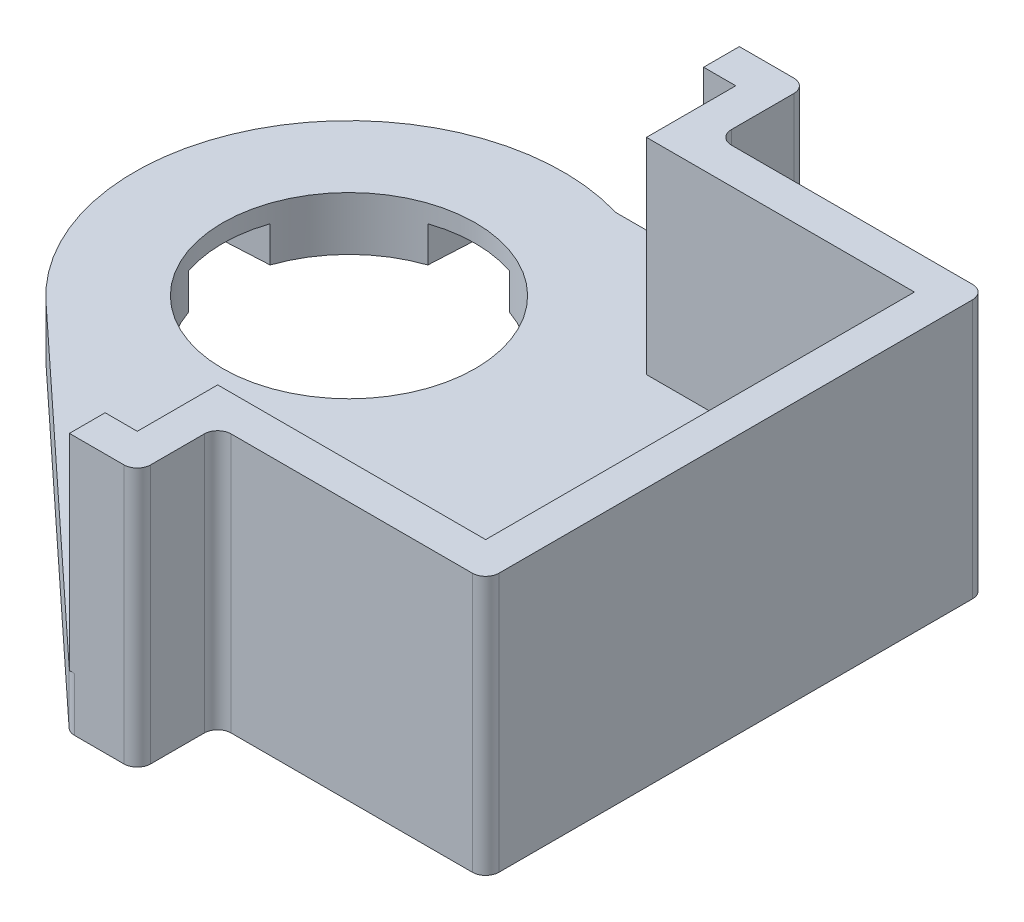
SolidWorks part; units mm, degrees
ref_plane "Front Plane" through (0, 0, 0) normal (0, 0, 1) x (1, 0, 0)
ref_plane "Top Plane" through (0, 0, 0) normal (0, 1, 0) x (1, 0, 0)
ref_plane "Right Plane" through (0, 0, 0) normal (1, 0, 0) x (0, 0, -1)
sketch "Sketch1" plane through (0, 0, 0) normal (0, 1, 0) x (1, 0, 0)
  line L0 (3.35, 28) -> (3.35, 23)
  line L9 (0, 0) -> (3.35, 0)
  line L10 (0, 0) -> (0, 23)
  line L11 (0, 23) -> (3.35, 23)
  line L12 (19.65, 0) -> (19.65, 23)
  line L14 (4.65, 0) -> (4.65, -5)
  line L15 (4.65, -5) -> (3.35, -5)
  line L16 (3.35, 0) -> (3.35, -5)
  line L17 (4.65, -5) -> (3.35, -5)
  line L18 (4.65, -5) -> (4.65, 28) construction
  line L19 (4.65, 28) -> (3.35, 28)
  line L20 (3.35, -5) -> (3.35, 28) construction
  line L21 (4.65, 28) -> (4.65, 23)
  line L22 (4.65, 0) -> (19.65, 0)
  line L23 (4.65, 23) -> (19.65, 23)
  line L24 (2.85, 28) -> (2.85, 23.5)
  line L25 (-0.5, 23.5) -> (2.85, 23.5)
  line L26 (-0.5, -0.5) -> (-0.5, 23.5)
  line L27 (-0.5, -0.5) -> (2.85, -0.5)
  line L28 (2.85, -0.5) -> (2.85, -5)
  line L29 (5.15, -0.5) -> (5.15, -5)
  line L30 (5.15, -0.5) -> (20.15, -0.5)
  line L31 (20.15, -0.5) -> (20.15, 23.5)
  line L32 (5.15, 23.5) -> (20.15, 23.5)
  line L33 (5.15, 28) -> (5.15, 23.5)
  line L34 (4.65, -4.5) -> (3.35, -4.5)
  line L35 (4.65, -4.5) -> (3.35, -4.5)
  line L37 (5.15, -5) -> (5.15, 28)
  line L38 (3.85, -5) -> (3.85, 28)
  line L39 (2.85, -5) -> (3.35, -5)
  line L40 (5.15, -5) -> (4.65, -5)
  line L41 (3.35, 28) -> (5.15, 28)
  line L42 (4.65, 28) -> (3.35, 28)
  line L43 (5.15, 28) -> (5.15, 28.5)
  line L46 (2.85, 28) -> (2.85, 28.5)
  line L47 (2.85, 28.5) -> (5.15, 28.5)
  line L48 (5.15, 28) -> (5.15, 28.5)
  dimension "D1" = 23
  dimension "D2" = 19.65
  dimension "D3" = 15
  dimension "D4" = 1.3
  dimension "D5" = 5
  dimension "D6" = 5
  dimension "D7" = 0.5
sketch "Sketch3" plane through (0, 0, 0) normal (0, 1, 0) x (1, 0, 0)
  line L1 (3.35, -5) -> (7.15, -5)
  line L2 (3.35, -5) -> (3.35, 28)
  line L3 (3.35, 28) -> (7.15, 28)
  line L4 (7.15, -5) -> (7.15, -2.5)
  line L5 (4.65, 28) -> (3.35, 28) construction
  line L6 (7.15, 25.5) -> (7.15, 28)
  line L7 (4.65, -5) -> (3.35, -5) construction
  line L8 (7.15, 25.5) -> (22.15, 25.5)
  line L10 (7.15, -2.5) -> (22.15, -2.5)
  line L11 (22.15, 25.5) -> (22.15, -2.5)
  line L12 (4.65, 23) -> (19.65, 23) construction
  line L13 (19.65, 0) -> (19.65, 23) construction
  line L14 (4.65, 0) -> (19.65, 0) construction
  line L15 (4.65, 0) -> (4.65, -5) construction
  point P20 (7.15, -3.75)
  dimension "D1" = 2.5
  dimension "D2" = 2.5
  dimension "D3" = 2.5
  dimension "D4" = 2.5
sketch "Sketch9" plane through (0, 0, 0) normal (0, 1, 0) x (1, 0, 0)
  line L0 (3.35, 28) -> (3.35, 23)
  line L9 (0, 0) -> (3.35, 0)
  line L10 (0, 0) -> (0, 23)
  line L11 (0, 23) -> (3.35, 23)
  line L12 (19.65, 0) -> (19.65, 23)
  line L14 (4.65, 0) -> (4.65, -4.5)
  line L15 (4.65, -5) -> (3.35, -5)
  line L16 (3.35, 0) -> (3.35, -4.5)
  line L17 (4.65, -5) -> (3.35, -5)
  line L18 (4.65, -4.5) -> (4.65, 28) construction
  line L19 (4.65, 28) -> (3.35, 28)
  line L20 (3.35, -4.5) -> (3.35, 28) construction
  line L21 (4.65, 28) -> (4.65, 23)
  line L22 (4.65, 0) -> (19.65, 0)
  line L23 (4.65, 23) -> (19.65, 23)
  line L24 (4.65, 28) -> (3.35, 28)
  line L25 (5.15, -5) -> (3.35, -5)
  line L26 (7.15, -5) -> (7.15, -6.25)
  line L27 (6.4, -7) -> (3.35, -7)
  line L28 (3.35, -5) -> (3.35, -7)
  line L29 (5.15, -0.5) -> (5.15, -5)
  line L30 (5.15, -0.5) -> (20.15, -0.5)
  line L31 (20.15, -0.5) -> (20.15, 23.5)
  line L32 (5.15, 23.5) -> (20.15, 23.5)
  line L33 (5.15, 28) -> (5.15, 23.5)
  line L34 (4.65, -4.5) -> (3.35, -4.5)
  line L35 (4.65, -4.5) -> (3.35, -4.5)
  line L36 (7.15, 28) -> (7.15, 26.25)
  line L37 (5.15, -5) -> (5.15, -0.5)
  line L38 (3.35, -5) -> (3.35, -7)
  line L40 (5.15, -5) -> (4.65, -5)
  line L41 (3.35, 28) -> (4.65, 28)
  line L42 (4.65, 28) -> (3.35, 28)
  line L43 (5.15, 28) -> (5.15, 28.5)
  line L47 (3.35, 30.5) -> (5.15, 30.5)
  line L48 (5.15, 28) -> (5.15, 28.5)
  line L49 (7.9, 25.5) -> (21.4, 25.5)
  line L50 (22.15, -1.75) -> (22.15, 24.75)
  line L51 (7.9, -2.5) -> (21.4, -2.5)
  line L52 (7.15, -3.25) -> (7.15, -5)
  line L53 (5.15, 23.5) -> (5.15, 28)
  line L54 (7.15, 28) -> (7.15, 29.75)
  line L55 (6.4, 30.5) -> (3.35, 30.5)
  line L57 (5.15, -5) -> (5.15, 28) construction
  line L58 (7.15, -2.5) -> (22.15, -2.5) construction
  line L60 (3.35, 30.5) -> (5.15, 30.5)
  line L61 (3.35, 30.5) -> (3.35, 28.5)
  line L62 (3.35, 28.5) -> (5.15, 28.5)
  line L64 (4.65, 0) -> (4.65, -5) construction
  line L65 (4.65, -5) -> (4.65, 28) construction
  line L66 (7.15, -2.5) -> (7.15, -5) construction
  line L67 (7.15, 28) -> (7.15, 25.5) construction
  line L68 (7.15, 25.5) -> (22.15, 25.5) construction
  line L69 (22.15, -2.5) -> (22.15, 25.5) construction
  arc A0 (7.9, -2.5) -> (7.15, -3.25) centre (7.9, -3.25) ccw
  arc A1 (7.15, 26.25) -> (7.9, 25.5) centre (7.9, 26.25) ccw
  arc A2 (7.15, 29.75) -> (6.4, 30.5) centre (6.4, 29.75) ccw
  arc A3 (21.4, 25.5) -> (22.15, 24.75) centre (21.4, 24.75) cw
  arc A4 (22.15, -1.75) -> (21.4, -2.5) centre (21.4, -1.75) cw
  arc A5 (7.15, -6.25) -> (6.4, -7) centre (6.4, -6.25) cw
  dimension "D10" = 0.75
  dimension "D1" = 23
  dimension "D2" = 19.65
  dimension "D3" = 15
  dimension "D4" = 1.3
  dimension "D5" = 5
  dimension "D6" = 5
  dimension "D7" = 0.5
  dimension "D8" = 2.5
  dimension "D9" = 2
  dimension "D11" = 0.5
extrude "Bracket" add sketch "Sketch9" along normal blind 11.5 contours L61 L62 L43 L33 L32 L31 L30 L29 L25 L15 L28 L27 L26 L52 L51 L50 L49 L36 L54 L55 L47 region at (4.9, 0, 5.4195)
sketch "Sketch12" plane through (0, 0, 0) normal (0, 1, 0) x (1, 0, 0)
  line L0 (3.1341, -6.7994) -> (-15.1691, 10.209)
  line L2 (-3.4667, 30.5) -> (6.4, 30.5)
  line L3 (7.15, 29.75) -> (7.15, 26.25)
  line L4 (7.9, 25.5) -> (21.4, 25.5)
  line L5 (22.15, 24.75) -> (22.15, -1.75)
  line L6 (21.4, -2.5) -> (7.9, -2.5)
  line L7 (7.15, -3.25) -> (7.15, -6.25)
  line L8 (6.4, -7) -> (3.6447, -7)
  arc A0 (-3.6746, 30.5294) -> (-15.1691, 10.209) centre (-7.0005, 18.9995) ccw
  arc A1 (3.1341, -6.7994) -> (3.6447, -7) centre (3.6447, -6.25) ccw
  arc A2 (7.15, -6.25) -> (6.4, -7) centre (6.4, -6.25) cw
  arc A3 (7.9, -2.5) -> (7.15, -3.25) centre (7.9, -3.25) ccw
  arc A4 (22.15, -1.75) -> (21.4, -2.5) centre (21.4, -1.75) cw
  arc A5 (21.4, 25.5) -> (22.15, 24.75) centre (21.4, 24.75) cw
  arc A6 (7.15, 26.25) -> (7.9, 25.5) centre (7.9, 26.25) ccw
  arc A7 (6.4, 30.5) -> (7.15, 29.75) centre (6.4, 29.75) cw
  arc A8 (-3.4667, 30.5) -> (-3.6746, 30.5294) centre (-3.4667, 31.25) cw
  point P17 (3.35, -7)
  point P22 (7.15, -2.5)
  point P25 (22.15, -2.5)
  point P28 (22.15, 25.5)
  point P31 (7.15, 25.5)
  dimension "D1" = 0.75
extrude "Boss-Extrude1" add sketch "Sketch12" against normal blind 3
sketch "Sketch15" plane through (0, 0, 0) normal (0, 1, 0) x (1, 0, 0)
  line L1 (-4.5, 21.5) -> (4.9995, 21.0005)
  line L2 (-7.0001, 21.5) -> (-7.0005, 30.9995)
  line L5 (-4.5, 21.5) -> (-9.5, 21.5)
  line L7 (-9.5, 21.5) -> (-9.0005, 30.9995)
  line L8 (-4.5, 21.5) -> (-5.0005, 30.9995)
  line L9 (-4.5, 16.5) -> (4.9995, 17.0005)
  line L10 (-4.5, 16.5) -> (-4.5, 21.5)
  line L11 (-4.5, 16.5) -> (-4.9995, 7.0005)
  line L12 (-9.5, 16.5) -> (-8.9995, 7.0005)
  line L13 (-9.5, 16.5) -> (-4.5, 16.5)
  line L14 (-9.5, 16.5) -> (-18.9995, 16.9995)
  line L15 (-9.5, 21.5) -> (-18.9995, 20.9995)
  line L16 (-9.5, 21.5) -> (-9.5, 16.5)
  circle A1 centre (-7, 19) radius 7.0711
  arc A6 (-3.6746, 30.5294) -> (-15.1691, 10.209) centre (-7.0005, 18.9995) ccw construction
  arc A7 (-9.0005, 30.9995) -> (-5.0005, 30.9995) centre (-7.0005, 30.9995) cw
  arc A8 (4.9995, 21.0005) -> (4.9995, 17.0005) centre (4.9995, 19.0005) cw
  arc A9 (-4.9995, 7.0005) -> (-8.9995, 7.0005) centre (-6.9995, 7.0005) cw
  arc A10 (-18.9995, 16.9995) -> (-18.9995, 20.9995) centre (-18.9995, 18.9995) cw
  point P0 (-7, 19)
  point P9 (-7, 19)
  point P12 (-7, 19)
  point P15 (-7, 19)
  point P18 (-7, 19)
  point P34 (-7, 19)
  dimension "D1" = 4
  dimension "D2" = 4
extrude "Cut-Extrude1" cut sketch "Sketch15" along normal blind 2 from surface contours A7 L7 A1 L8 | A10 L14 A1 L15 | A9 L11 A1 L12 | L9 A1 L1 L10 | A8 L1 A1 L9 | A1 | L9 A8 L1 L10 region at (-2.3114, 0, -19.0001) region at (3.1936, 0, -19.0004) region at (-7.0004, 0, -29.1936) region at (-6.9996, 0, -8.8064) region at (-17.1936, 0, -18.9996) starting at face at (7.1197, -3, -11.8189)
extrude "Cut-Extrude2" cut sketch "Sketch15<4>" against normal blind 2.5 contours L7 A1 L15 | L2 A1 L7 L5 | L8 A1 L2 L5 | L1 A1 L8 | L11 A1 L9 | L9 A1 L1 L10 | L5 L16 L13 L10 | L12 A1 L11 L13 | L15 A1 L14 L16 | L14 A1 L12 region at (-2.9514, 0, -23.0488) region at (-7, 0, -19) region at (-5.8229, 0, -23.6886) region at (-2.3114, 0, -19.0001) region at (-8.1774, 0, -23.6886) region at (-2.9512, 0, -14.9514) region at (-6.9999, 0, -14.3114) region at (-11.0488, 0, -23.0486) region at (-11.6886, 0, -18.9999) region at (-11.0486, 0, -14.9512)
sketch "Sketch15<4>" plane through (0, 0, 0) normal (0, 1, 0) x (1, 0, 0) same geometry as "Sketch15"
